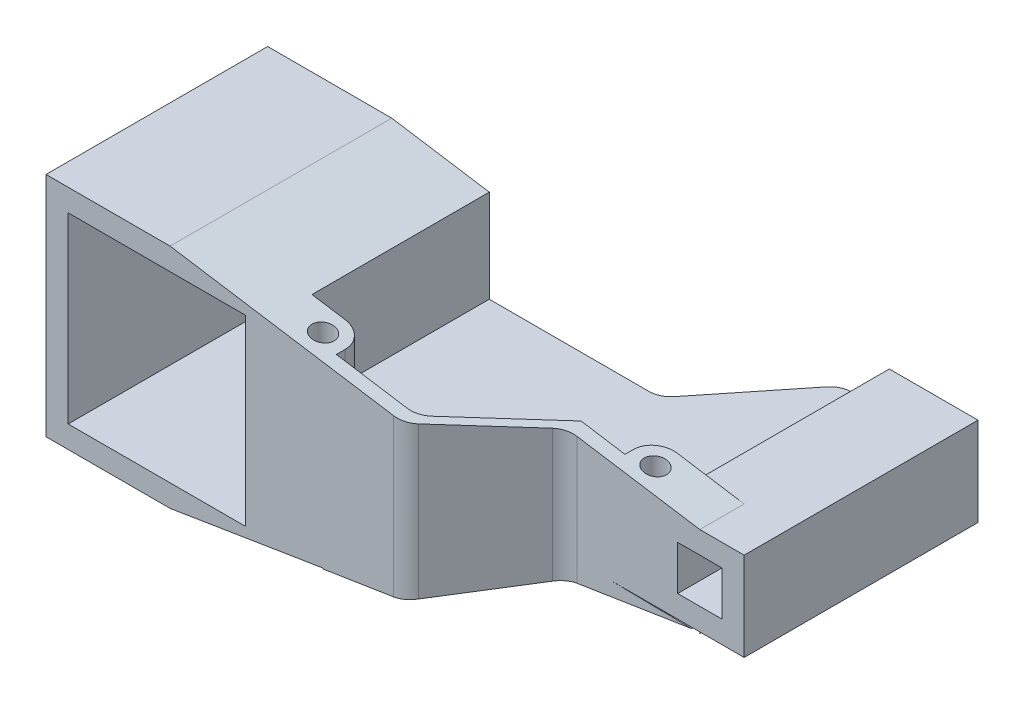
SolidWorks part; units mm, degrees
material "Alliage 1060"
ref_plane "Plan de face" through (0, 0, 0) normal (0, 0, 1) x (1, 0, 0)
ref_plane "Plan de dessus" through (0, 0, 0) normal (0, 1, 0) x (1, 0, 0)
ref_plane "Plan de droite" through (0, 0, 0) normal (1, 0, 0) x (0, 0, -1)
sketch "Esquisse1" plane through (0, 0, 0) normal (0, 0, 1) x (1, 0, 0)
  line L0 (-82.9485, -51.25) -> (116.0515, -20)
  line L5 (-138.9485, -51.25) -> (-38.9485, -51.25)
  line L6 (-138.9485, -51.25) -> (-138.9485, 51.25)
  line L11 (-138.9485, 51.25) -> (-38.9485, 51.25)
  line L12 (-38.9485, -51.25) -> (-38.9485, 51.25)
  line L17 (-82.9485, 51.25) -> (116.0515, 20)
  line L18 (-138.9485, 51.25) -> (-38.9485, -51.25) construction
  line L19 (-128.9485, -41.25) -> (-48.9485, -41.25)
  line L20 (-128.9485, -41.25) -> (-128.9485, 41.25)
  line L21 (-128.9485, 41.25) -> (-48.9485, 41.25)
  line L22 (-48.9485, -41.25) -> (-48.9485, 41.25)
  line L23 (-128.9485, -41.25) -> (-48.9485, 41.25) construction
  line L24 (-128.9485, 41.25) -> (-48.9485, -41.25) construction
  line L25 (106.0515, -10) -> (126.0515, -10)
  line L26 (106.0515, -10) -> (106.0515, 10)
  line L27 (106.0515, 10) -> (126.0515, 10)
  line L28 (126.0515, -10) -> (126.0515, 10)
  line L29 (106.0515, -10) -> (126.0515, 10) construction
  line L30 (106.0515, 10) -> (126.0515, -10) construction
  line L31 (96.0515, -20) -> (136.0515, -20)
  line L32 (96.0515, -20) -> (96.0515, 20)
  line L33 (96.0515, 20) -> (136.0515, 20)
  line L34 (136.0515, -20) -> (136.0515, 20)
  line L35 (96.0515, -20) -> (136.0515, 20) construction
  line L36 (96.0515, 20) -> (136.0515, -20) construction
  point P0 (-88.9485, 0)
  point P1 (116.0515, 0)
  point P2 (116.0515, 0)
  point P3 (-88.9485, 0)
  point P8 (-88.9485, 0)
  point P17 (116.0515, 0)
  point P22 (-82.9485, 51.25)
  point P23 (-82.9485, -51.25)
  dimension "D3" = 205
  dimension "D4" = 102.5
  dimension "D5" = 100
  dimension "D6" = 10
  dimension "D7" = 10
  dimension "D8" = 10
  dimension "D9" = 6
  dimension "D10" = 6
  dimension "D11" = 40
  dimension "D12" = 40
  dimension "D13" = 20
  dimension "D14" = 20
extrude "Boss.-Extru.3" add sketch "Esquisse1" along normal blind 100 contours L17 L11 L6 L5 L0 L12 L22 L19 L20 L21 region at (-110.9485, -49.818, 0)
sketch "Esquisse2" plane through (0, 51.25, 0) normal (0, 1, 0) x (1, 0, 0)
  line L0 (-138.9485, -100) -> (-138.9485, 0) construction
  line L2 (-82.9485, -100) -> (-38.9485, -100) construction
  line L4 (-38.9485, -100) -> (-13.9485, -100)
  line L5 (-38.9485, -100) -> (-38.9485, -80)
  line L6 (-38.9485, -80) -> (-13.9485, -80)
  line L7 (-13.9485, -100) -> (-13.9485, -80)
  point P0 (-23.9485, -90)
  dimension "D1" = 115
  dimension "D2" = 10
extrude "Boss.-Extru.4" add sketch "Esquisse2" against normal through all
sketch "Esquisse4" plane through (0, 0, 80) normal (0, 0, -1) x (-1, 0, 0)
  line L0 (82.9485, 51.25) -> (7.1014, 39.733)
  line L1 (7.1014, 39.733) -> (13.4611, 66.0388)
  line L2 (13.4611, 66.0388) -> (82.9485, 62.2808)
  line L3 (82.9485, 62.2808) -> (82.9485, 51.25)
  line L4 (82.9485, -51.25) -> (-9.3758, -36.2935)
  line L5 (-9.3758, -36.2935) -> (26.7585, -73.5841)
  line L6 (26.7585, -73.5841) -> (82.9485, -51.25)
extrude "Enlèv. mat.-Extru.1" cut sketch "Esquisse4" against normal through all contours L3 L0 L1 L2 | L6 L4 L5
sketch "Esquisse5" plane through (0, 0, 80) normal (0, 0, -1) x (-1, 0, 0)
  line L0 (138.9485, -51.25) -> (82.9485, -51.25) construction
  line L1 (138.9485, 51.25) -> (82.9485, 51.25) construction
  line L2 (38.9485, -44.3405) -> (38.9485, 44.3405) construction
  line L3 (38.9485, 2.5) -> (13.9485, 2.5)
  line L4 (38.9485, 2.5) -> (38.9485, -2.5)
  line L5 (38.9485, -2.5) -> (13.9485, -2.5)
  line L6 (13.9485, 2.5) -> (13.9485, -2.5)
  line L7 (13.9485, -40.072) -> (13.9485, 40.7727) construction
  point P0 (37.8311, -2.5)
  point P1 (37.8311, 2.5)
  dimension "D1" = 48.75
  dimension "D2" = 48.75
extrude "Boss.-Extru.6" add sketch "Esquisse5" along normal blind 80
sketch "Esquisse6" plane through (0, 51.25, 0) normal (0, 1, 0) x (1, 0, 0)
  line L0 (-38.9485, -100) -> (-13.9485, -100) construction
  line L1 (-138.9485, -100) -> (-138.9485, 0) construction
  circle A0 centre (-23.9485, -90) radius 5
  point P0 (-23.9485, -90)
  dimension "D3" = 10
  dimension "D1" = 10
  dimension "D2" = 115
extrude "Enlèv. mat.-Extru.2" cut sketch "Esquisse6" against normal through all
fillet "Congé1" radius 10 2 edges at (-13.9485, -21.286, 80) (-13.9485, 21.6364, 80)
sketch "Esquisse7" plane through (0, 0, 0) normal (0, 0, -1) x (-1, 0, 0)
  line L0 (128.9485, 41.25) -> (48.9485, -41.25)
  line L1 (-106.0515, -10) -> (-126.0515, -10)
  line L2 (-106.0515, -10) -> (-106.0515, 10)
  line L3 (-106.0515, 10) -> (-126.0515, 10)
  line L4 (-126.0515, -10) -> (-126.0515, 10)
  line L5 (-106.0515, -10) -> (-126.0515, 10) construction
  line L6 (-106.0515, 10) -> (-126.0515, -10) construction
  line L7 (-96.0515, -20) -> (-136.0515, -20)
  line L8 (-96.0515, -20) -> (-96.0515, 20)
  line L9 (-96.0515, 20) -> (-136.0515, 20)
  line L10 (-136.0515, -20) -> (-136.0515, 20)
  line L11 (-96.0515, -20) -> (-136.0515, 20) construction
  line L12 (-96.0515, 20) -> (-136.0515, -20) construction
  line L13 (48.9485, 41.25) -> (128.9485, -41.25)
  line L14 (88.9485, 0) -> (-116.0515, 0)
  point P0 (-116.0515, 0)
  point P5 (-116.0515, 0)
  dimension "D1" = 205
  dimension "D2" = 40
  dimension "D3" = 40
  dimension "D4" = 20
  dimension "20" = 20
extrude "Boss.-Extru.7" add sketch "Esquisse7" against normal blind 156 and the other way blind 132 separate body contours L10 L7 L8 L2 L1 L4 L3 L9 region at (96.6172, -10, 0)
sketch "Esquisse8" plane through (0, 51.25, 0) normal (0, 1, 0) x (1, 0, 0)
  line L0 (-82.9485, -100) -> (-38.9485, -100) construction
  line L1 (-68.2574, -100) -> (171.4967, -100)
  line L2 (-68.2574, -100) -> (-68.2574, -60)
  line L3 (-68.2574, -60) -> (171.4967, -60)
  line L4 (171.4967, -100) -> (171.4967, -60)
  line L5 (96.0515, 132) -> (96.0515, -156) construction
  line L6 (96.0515, -60) -> (153.0176, -60)
  line L7 (96.0515, -60) -> (96.0515, -172.152)
  line L8 (96.0515, -172.152) -> (153.0176, -172.152)
  line L9 (153.0176, -60) -> (153.0176, -172.152)
  dimension "D1" = 40
extrude "Enlèv. mat.-Extru.3" cut sketch "Esquisse8" against normal through all contours L9 L1 L7 L8 | L9 L3 L7 L1 region at (124.5346, 51.25, 80) region at (124.5346, 51.25, 136.076)
sketch "Esquisse9" plane through (0, 20, 0) normal (0, 1, 0) x (1, 0, 0)
  line L0 (136.0515, 132) -> (136.0515, -60) construction
  line L1 (96.0515, -60) -> (136.0515, -60)
  line L2 (96.0515, -60) -> (96.0515, 45.5)
  line L3 (96.0515, 45.5) -> (136.0515, 45.5)
  line L4 (136.0515, -60) -> (136.0515, 45.5)
  line L6 (96.0515, 45.5) -> (136.0515, 45.5)
  line L7 (96.0515, 45.5) -> (96.0515, 145.393)
  line L8 (96.0515, 145.393) -> (136.0515, 145.393)
  line L9 (136.0515, 45.5) -> (136.0515, 145.393)
  line M6 (136.0515, -60) -> (136.0515, 132)
  line M7 (136.0515, 132) -> (96.0515, 132)
  line M8 (96.0515, 132) -> (96.0515, -60)
  dimension "D1" = 105.5
extrude "Enlèv. mat.-Extru.4" cut sketch "Esquisse9" against normal through all contours L3 M8 M6 M7 region at (116.0515, 20, -88.75)
sketch "Esquisse10" plane through (0, 20, 0) normal (0, 1, 0) x (1, 0, 0)
  line L0 (136.0515, -60) -> (96.0515, -60) construction
  line L2 (96.0515, -60) -> (76.0515, -60)
  line L3 (96.0515, -60) -> (96.0515, -40)
  line L4 (96.0515, -40) -> (76.0515, -40)
  line L5 (76.0515, -60) -> (76.0515, -40)
  point P0 (86.0515, -50)
  dimension "D1" = 10
  dimension "D2" = 50
  dimension "D3" = 20
  dimension "D4" = 10
extrude "Boss.-Extru.9" add sketch "Esquisse10" against normal blind 40
sketch "Esquisse11" plane through (0, 0, -45.5) normal (0, 0, -1) x (-1, 0, 0)
  line L0 (-96.0515, -20) -> (-96.0515, 20) construction
  line L1 (-96.0515, -20) -> (-96.0515, 20) construction
  line L2 (-96.0515, 20) -> (-136.0515, 20) construction
  line L3 (-136.0515, -20) -> (-96.0515, -20) construction
  line L4 (-76.0515, -20) -> (-76.0515, 20) construction
  line L5 (-96.0515, 2.5) -> (-76.0515, 2.5)
  line L6 (-96.0515, 2.5) -> (-96.0515, -2.5)
  line L7 (-96.0515, -2.5) -> (-76.0515, -2.5)
  line L8 (-76.0515, 2.5) -> (-76.0515, -2.5)
  point P0 (-96.0515, 2.5)
  point P1 (-96.0515, -2.5)
  dimension "D1" = 17.5
  dimension "D2" = 17.5
extrude "Boss.-Extru.10" add sketch "Esquisse11" against normal up to next
sketch "Esquisse13" plane through (0, 0, 60) normal (0, 0, 1) x (1, 0, 0)
  line L0 (136.0515, 20) -> (76.0515, 20) construction
  line L1 (136.0515, 20) -> (136.0515, -20) construction
  line L3 (-80.7222, 50.9004) -> (116.0515, 20)
  line L4 (-82.9485, 51.25) -> (-38.9485, 44.3405) construction
  line L5 (-82.9485, -51.25) -> (116.0515, -20.6269)
  line L6 (-82.9485, -51.25) -> (-13.9485, -40.072) construction
  line L7 (-138.9485, -51.25) -> (-82.9485, -51.25) construction
  line L8 (116.0515, -20.6269) -> (75.5108, -26.8655)
  line L9 (116.0515, 20) -> (76.0515, 20)
  line L10 (76.0515, 20) -> (76.0515, 26.2814)
  line L11 (116.0515, -20.6269) -> (76.0515, -20)
  line L12 (76.0515, -20) -> (75.5108, -26.8655)
  point P0 (116.0515, 20)
  point P1 (116.0515, -20.6269)
  line M6 (136.0515, 20) -> (76.0515, 20)
  dimension "D1" = 20
  dimension "D2" = 20
extrude "Boss.-Extru.11" add sketch "Esquisse13" against normal blind 20 contours L10 L3 M6 | L11 L12 L8 region at (89.3849, 22.0938, 60)
sketch "Esquisse14" plane through (0, 51.25, 0) normal (0, 1, 0) x (1, 0, 0)
  line L0 (76.0515, -60) -> (116.0515, -60) construction
  line L1 (136.0515, 45.5) -> (136.0515, -60) construction
  circle A0 centre (86.0515, -50) radius 5
  point P0 (86.0515, -50)
  dimension "D3" = 10
  dimension "D1" = 10
  dimension "D2" = 50
extrude "Enlèv. mat.-Extru.5" cut sketch "Esquisse14" against normal through all
fillet "Congé2" radius 10 1 edges at (76.0515, -11.25, 40)
fillet "Congé3" radius 10 1 edges at (75.7812, -23.4328, 40)
sketch "Esquisse21" plane through (0, 51.25, 0) normal (0, 1, 0) x (1, 0, 0)
  line L0 (-38.9485, -100) -> (-13.9485, -100) construction
  line L1 (76.0515, -60) -> (116.0515, -60) construction
  line L2 (25.4849, -90.4279) -> (56.0515, -54)
  line L3 (13.5847, -94) -> (-13.9485, -94)
  line L4 (-13.9485, -90) -> (-13.9485, -100) construction
  line L5 (-13.9485, -94) -> (17.8245, -94)
  line L8 (-13.9485, -100) -> (-13.9485, -94)
  line L9 (56.0515, -60) -> (25.4849, -96.4279)
  line L10 (-13.9485, -100) -> (17.8245, -100)
  line L11 (-13.9485, -94) -> (-13.9485, -97)
  line L12 (40.7682, -72.2139) -> (43.6973, -74.7231)
  arc A0 (17.8245, -94) -> (25.4849, -90.4279) centre (17.8245, -84) ccw
  arc A1 (25.4849, -96.4279) -> (17.8245, -100) centre (17.8245, -90) cw
  point P0 (13.5847, -100)
  point P1 (56.0515, -60)
  point P2 (56.0515, -54)
  point P3 (13.5847, -94)
  dimension "D2" = 10
  dimension "D1" = 0
  dimension "D3" = 0
  dimension "D4" = 80
extrude "Boss.-Extru.30" add sketch "Esquisse21" against normal through all contours A1 L9 L12 L2 A0 L5 L3 L8 L10 region at (33.6168, 51.25, 81.7322)
sketch "Esquisse27" plane through (0, 0, 40) normal (0, 0, -1) x (-1, 0, 0)
  line L1 (-76.0515, 55.5321) -> (-38.0996, 55.5321)
  line L2 (-76.0515, 55.5321) -> (-76.0515, -56.8504)
  line L3 (-76.0515, -56.8504) -> (-38.0996, -56.8504)
  line L4 (-38.0996, 55.5321) -> (-38.0996, -56.8504)
extrude "Boss.-Extru.49" add sketch "Esquisse27" against normal through all
sketch "Esquisse28" plane through (0, 55.5321, 0) normal (0, 1, 0) x (1, 0, 0)
  line L0 (53.0541, -63.5721) -> (31.7922, -88.9111)
  line L1 (136.0515, -60) -> (60.7146, -60)
  line L2 (38.0996, -81.3943) -> (25.4849, -96.4279) construction
  line L3 (31.7922, -88.9111) -> (38.0996, -81.3943)
  line L4 (38.0996, -81.3943) -> (38.0996, -105.5222)
  line L5 (38.0996, -105.5222) -> (75.9998, -105.5222)
  line L6 (75.9998, -105.5222) -> (76.0515, -60)
  arc A0 (60.7146, -60) -> (53.0541, -63.5721) centre (60.7146, -70) ccw
  line M2 (38.0996, -40) -> (38.0996, -100)
  line M3 (38.0996, -100) -> (76.0515, -100)
  dimension "D1" = 10
extrude "Enlèv. mat.-Extru.8" cut sketch "Esquisse28" against normal through all contours L1 A0 L0 L6 M2 M3 region at (58.9511, 55.5321, 81.9082)
sketch "Esquisse29" plane through (0, 55.5321, 0) normal (0, 1, 0) x (1, 0, 0)
  line L0 (76.0515, -60) -> (60.7146, -60) construction
  line L1 (68.3831, -60) -> (86.546, -60)
  line L2 (68.3831, -60) -> (68.3831, -108.4883)
  line L3 (68.3831, -108.4883) -> (86.546, -108.4883)
  line L4 (86.546, -60) -> (86.546, -108.4883)
extrude "Enlèv. mat.-Extru.9" cut sketch "Esquisse29" against normal through all
sketch "Esquisse33" plane through (0, -20, 0) normal (0, -1, 0) x (1, 0, 0)
  line L0 (27.0472, 88.566) -> (73.8347, 32.8069)
  line L1 (25.4849, 90.4279) -> (38.0996, 75.3943) construction
  line L2 (73.8347, 32.8069) -> (27.0472, 32.8069)
  line L3 (27.0472, 32.8069) -> (27.0472, 88.566)
extrude "Enlèv. mat.-Extru.15" cut sketch "Esquisse33" along normal through all and the other way blind 104
sketch "Esquisse34" plane through (0, 2.5, 0) normal (0, 1, 0) x (1, 0, 0)
  line L0 (136.0515, -60) -> (116.0515, -60) construction
  point P0 (127.7419, -54)
  dimension "D1" = 6
sketch "Esquisse36" plane through (0, -51.25, 0) normal (0, -1, 0) x (1, 0, 0)
  line L8 (51.6119, 53.7802) -> (51.6119, 26.0965)
  line L17 (51.6119, 53.7802) -> (79.6251, 53.7802)
  line L18 (79.6251, 53.7802) -> (79.6251, 20.1643)
  line L19 (79.6251, 20.1643) -> (51.6119, 20.1643)
  line L20 (51.6119, 20.1643) -> (51.6119, 28.4035)
extrude "Enlèv. mat.-Extru.25" cut sketch "Esquisse36" against normal through all contours L20 L19 L18 L17 L8 region at (65.6185, -51.25, 36.9722)
sketch "Esquisse46" plane through (0, 0, -45.5) normal (0, 0, -1) x (-1, 0, 0)
  line L0 (-116.0515, 20) -> (82.9485, 51.25)
  line L1 (-96.0515, 20) -> (-136.0515, 20) construction
  line L2 (82.9485, 51.25) -> (-79.9546, 76.954)
  line L3 (-79.9546, 76.954) -> (-116.0515, 20)
extrude "Enlèv. mat.-Extru.33" cut sketch "Esquisse46" against normal blind 157
sketch "Esquisse47" plane through (0, 0, -45.5) normal (0, 0, -1) x (-1, 0, 0)
  line L0 (-82.645, -25.7677) -> (82.9485, -51.25)
  line L1 (-85.6649, -25.303) -> (-79.6251, -26.2324) construction
  line L2 (138.9485, -51.25) -> (82.9485, -51.25) construction
  line L3 (82.9485, -51.25) -> (-105.3313, -68.5489)
  line L4 (-105.3313, -68.5489) -> (-82.645, -25.7677)
extrude "Enlèv. mat.-Extru.34" cut sketch "Esquisse47" against normal blind 157
sketch "Esquisse48" plane through (0, 0, 0) normal (0, 0, -1) x (-1, 0, 0)
  line L1 (-76.0515, -2.5) -> (13.9485, -2.5)
  line L2 (-76.0515, -2.5) -> (-76.0515, 2.5)
  line L3 (-76.0515, 2.5) -> (13.9485, 2.5)
  line L4 (13.9485, -2.5) -> (13.9485, 2.5)
extrude "Boss.-Extru.60" add sketch "Esquisse48" against normal up to next
sketch "Esquisse49" plane through (0, -2.5, 0) normal (0, -1, 0) x (1, 0, 0)
  line L0 (79.6251, 53.7802) -> (56.236, 53.7802) construction
  line L1 (75.3407, 53.7802) -> (79.6251, 53.7802)
  line L2 (75.3407, 53.7802) -> (75.3407, 20.1643)
  line L3 (75.3407, 20.1643) -> (79.6251, 20.1643)
  line L4 (79.6251, 53.7802) -> (79.6251, 20.1643)
extrude "Boss.-Extru.61" add sketch "Esquisse49" against normal blind 5
sketch "Esquisse51" plane through (0, 20, 0) normal (0, 1, 0) x (1, 0, 0)
  line L0 (76.0515, -40) -> (76.0515, -53.7802)
  line L5 (56.236, -53.7802) -> (79.6251, -53.7802) construction
  line L6 (76.0515, -53.7802) -> (79.6251, -53.7802)
  line L7 (79.6251, -53.7802) -> (79.6251, -42.3384)
  line L8 (79.6251, -42.3384) -> (79.6251, -53.7802) construction
  line L9 (79.6251, -53.7802) -> (79.6251, -42.3384) construction
  line L10 (79.6251, -42.3384) -> (86.0515, -42.3384)
  line L11 (86.0515, -42.3384) -> (86.0515, -40)
  line L12 (86.0515, -40) -> (76.0515, -40)
extrude "Boss.-Extru.63" add sketch "Esquisse51" against normal blind 17.5 and the other way blind 44
sketch "Esquisse53" plane through (0, 0, 100) normal (0, 0, 1) x (1, 0, 0)
  line L0 (-80.0958, 50.802) -> (116.0515, 20)
  line L1 (-82.9485, 51.25) -> (17.8245, 35.4251) construction
  line L2 (116.0515, 20) -> (116.0515, 87.2838)
  line L3 (116.0515, 87.2838) -> (-75.4097, 80.6433)
  line L4 (-75.4097, 80.6433) -> (-80.0958, 50.802)
extrude "Enlèv. mat.-Extru.35" cut sketch "Esquisse53" against normal through all
fillet "Congé5" radius 10 1 edges at (76.0515, 14.3907, 40)
ref_plane "Plan6" through (136.0515, -20, -45.5) normal (0, 0, 1) x (1, 0, 0)
sketch "Esquisse68" plane through (0, -2.5, 0) normal (0, -1, 0) x (1, 0, 0)
  line L0 (76.0515, 53.7802) -> (76.0515, 40)
  line L2 (79.6251, 53.7802) -> (56.236, 53.7802) construction
  line L3 (76.0515, 53.7802) -> (79.6251, 53.7802)
  line L4 (79.6251, 53.7802) -> (79.6251, 44.2227)
  line L5 (79.6251, 41.9614) -> (79.6251, 53.7802) construction
  line L6 (79.6251, 44.2227) -> (91.0515, 40)
  line L7 (86.0515, 40) -> (96.0515, 40) construction
  line L8 (91.0515, 40) -> (76.0515, 40)
extrude "Boss.-Extru.70" add sketch "Esquisse68" along normal blind 15.5
fillet "Congé6" radius 10 1 edges at (76.0515, -10.25, 40)
sketch "Esquisse70" plane through (0, 0, 40) normal (0, 0, -1) x (-1, 0, 0)
  line L0 (-79.6251, -26.2324) -> (-56.236, -29.8316) construction
  line L1 (-89.5121, -14.9953) -> (-76.1876, -14.9953)
  line L2 (-89.5121, -14.9953) -> (-89.5121, -26.7614)
  line L3 (-89.5121, -26.7614) -> (-76.1876, -26.7614)
  line L4 (-76.1876, -14.9953) -> (-76.1876, -26.7614)
extrude "Boss.-Extru.72" add sketch "Esquisse70" against normal blind 5
sketch "Esquisse71" plane through (0, 0, 40) normal (0, 0, -1) x (-1, 0, 0)
  line L0 (-76.1876, -14.9953) -> (-86.0515, -14.9953) construction
  line L1 (-81.1195, -14.9953) -> (-76.1876, -14.9953)
  line L2 (-81.1195, -14.9953) -> (-81.1195, -26.7614)
  line L3 (-81.1195, -26.7614) -> (-76.1876, -26.7614)
  line L4 (-76.1876, -14.9953) -> (-76.1876, -26.7614)
extrude "Boss.-Extru.73" add sketch "Esquisse71" against normal blind 15
fillet "Congé7" radius 10 1 edges at (76.1876, -20.8783, 40)
sketch "Esquisse73" plane through (0, 0, -45.5) normal (0, 0, -1) x (-1, 0, 0)
  line L0 (-116.0515, -20) -> (82.9485, -51.25)
  line L1 (-136.0515, -20) -> (-96.0515, -20) construction
  line L2 (82.9485, -51.25) -> (-108.627, -51.25)
  line L3 (-108.627, -51.25) -> (-116.0515, -20)
extrude "Enlèv. mat.-Extru.36" cut sketch "Esquisse73" against normal through all
sketch "Esquisse75" plane through (0, 0, -45.5) normal (0, 0, -1) x (-1, 0, 0)
  line L0 (-76.0515, 2.5) -> (-86.0515, 2.5) construction
  line L1 (-76.0515, 2.5) -> (-25.4849, 2.5)
  line L2 (-76.0515, 2.5) -> (-76.0515, -2.5)
  line L3 (-76.0515, -2.5) -> (-25.4849, -2.5)
  line L4 (-25.4849, 2.5) -> (-25.4849, -2.5)
  line L5 (-76.0515, -2.5) -> (-76.0515, 2.5) construction
  line L6 (-25.4849, -2.5) -> (-17.8245, -2.5) construction
  line L7 (-76.0515, -2.5) -> (38.9485, -2.5) construction
extrude "Boss.-Extru.74" add sketch "Esquisse75" against normal up to next
sketch "Esquisse76" plane through (0, 2.5, 0) normal (0, 1, 0) x (1, 0, 0)
  line L0 (40.9148, 3.753) -> (74.9713, 46.3236)
  line L2 (53.0541, -63.5721) -> (25.4849, -96.4279) construction
  line L3 (25.4849, 0) -> (33.1061, 0)
  line L4 (25.4849, 0) -> (25.4849, 45.5)
  line L5 (25.4849, 45.5) -> (74.9713, 46.3236)
  arc A0 (33.1061, 0) -> (40.9148, 3.753) centre (33.1061, 10) ccw
  point P2 (5.5233, -40.4864)
  dimension "D2" = 10
  dimension "D1" = 51.25
extrude "Enlèv. mat.-Extru.37" cut sketch "Esquisse76" along normal through all and the other way blind 60 contours L0 L5 L4 L3 A0
fillet "Congé8" radius 10 1 edges at (74.3124, 0, -45.5)
equation "\"A\"= 205"
equation "\"B\"= 100"
equation "\"W\"= 50"
equation "\"X\"= 51.25"
equation "\"Y\"= 105.5"
equation "\"Z\"= 115"
equation "\"2X\"= 102.5"
equation "\"D3@Esquisse1\"=\"A\""
equation "\"D4@Esquisse1\"=\"2X\""
equation "\"D5@Esquisse1\"=\"B\""
equation "\"D1@Esquisse2\"=\"Z\""
equation "\"D2@Esquisse6\"=\"Z\""
equation "\"D1@Esquisse7\"=\"A\""
equation "\"D1@Esquisse9\"=\"Y\""
equation "\"D1@Esquisse76\"=\"X\""
